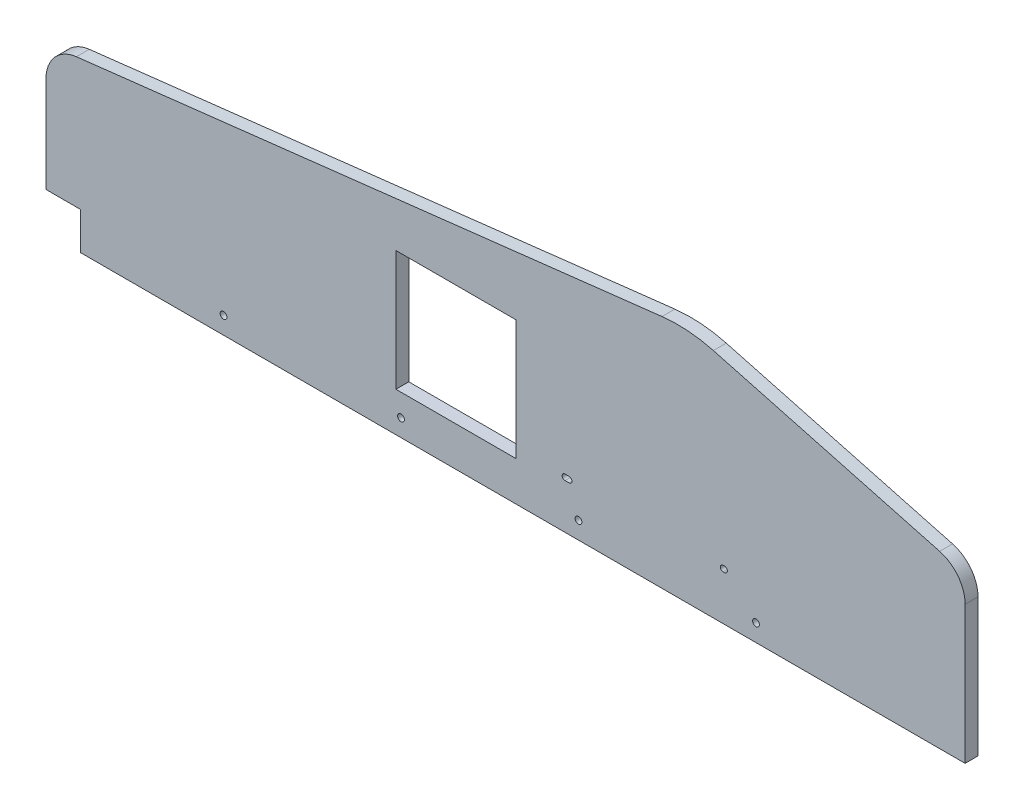
SolidWorks part; units mm, degrees
material "PC High Viscosity"
ref_plane "Front Plane" through (0, 0, 0) normal (0, 0, 1) x (1, 0, 0)
ref_plane "Top Plane" through (0, 0, 0) normal (0, 1, 0) x (1, 0, 0)
ref_plane "Right Plane" through (0, 0, 0) normal (1, 0, 0) x (0, 0, -1)
sketch "Sketch2" plane through (0, 0, 0) normal (0, 0, 1) x (1, 0, 0)
  line L0 (-340, 26.4) -> (-340, 121.4)
  line L1 (-340, 121.4) -> (135, 176.4)
  line L2 (135, 176.4) -> (340, 121.4)
  line L3 (340, 121.4) -> (340, 26.4)
  line L4 (340, 26.4) -> (340, 0)
  line L6 (340, 0) -> (-340, 0)
  line L7 (-340, 0) -> (-340, 26.4)
  dimension "D1" = 150
  dimension "D2" = 680
  dimension "D3" = 95
  dimension "D4" = 475
  dimension "D8" = 95
  dimension "D9" = 26.4
extrude "Boss-Extrude1" add sketch "Sketch2" along normal mid plane 9.525
fillet "Fillet1" radius 25.4 2 edges at (340, 121.4, 0) (-340, 121.4, 0)
fillet "Fillet2" radius 101.6 1 edges at (135, 176.4, 0)
sketch "Sketch3" plane through (0, 0, 4.7625) normal (0, 0, 1) x (1, 0, 0)
  line L0 (0, 0) -> (0, 192.0016) construction
  line L1 (-340, 0) -> (-314.6, 0)
  line L2 (-340, 0) -> (-340, 27.686)
  line L3 (-340, 27.686) -> (-314.6, 27.686)
  line L4 (-314.6, 0) -> (-314.6, 27.686)
  line L5 (0, 192.0016) -> (0, -60.0751) construction
  dimension "D1" = 25.4
  dimension "D2" = 27.686
extrude "Cut-Extrude1" cut sketch "Sketch3" against normal through all
sketch "Sketch5" plane through (0, 0, 4.7625) normal (0, 0, 1) x (1, 0, 0)
  line L0 (-314.6, 0) -> (340, 0) construction
  line L3 (-81.1185, 29.1465) -> (7.7815, 29.1465)
  line L5 (7.7815, 29.1465) -> (7.7815, 118.0465)
  line L6 (7.7815, 118.0465) -> (-81.1185, 118.0465)
  line L7 (340, 0) -> (340, 101.9164) construction
  line L8 (-81.1185, 29.1465) -> (-81.1185, 118.0465)
  dimension "D1" = 332.2185
  dimension "D3" = 29.1465
extrude "Cut-Extrude2" cut sketch "Sketch5" against normal through all
hole_wizard "Tap Drill for M6x1.0 Tap1" positions "Sketch7" profile "Sketch6" hole size "M6x1.0" standard "ANSI Metric" end condition through all
sketch "Sketch7" plane through (0, 0, 4.7625) normal (0, 0, 1) x (1, 0, 0)
  line L0 (-314.6, 0) -> (340, 0) construction
  line L1 (-340, 98.7713) -> (-340, 27.686) construction
  point P0 (-208.682, 12.7)
  point P2 (-77.364, 12.7)
  point P4 (53.954, 12.7)
  point P6 (185.272, 12.7)
  dimension "D1" = 12.7
  dimension "D2" = 131.318
  dimension "D3" = 131.318
  dimension "D4" = 131.318
  dimension "D5" = 131.318
sketch "Sketch6" plane through (-208.682, 12.7, 4.7625) normal (1, 0, 0) x (0, -1, 0)
  line L0 (0, 0) -> (0, 9.525)
  line L1 (0, 9.525) -> (2.5, 9.525)
  line L2 (2.5, 9.525) -> (2.5, 0)
  line L5 (2.5, 0) -> (0, 0)
  line L11 (0, -6.35) -> (0, 107.95) construction
  dimension "Thru Hole Dia." = 5
  dimension "Thru Hole Depth" = 9.525
sketch "Sketch8" plane through (0, 0, 4.7625) normal (0, 0, 1) x (1, 0, 0)
  line L0 (161, 35.3) -> (162, 35.3) construction
  line L1 (161, 37.4) -> (162, 37.4)
  line L2 (161, 33.2) -> (162, 33.2)
  line L3 (47, 35.3) -> (44, 35.3) construction
  line L4 (47, 33.2) -> (44, 33.2)
  line L5 (47, 37.4) -> (44, 37.4)
  line L6 (-314.6, 0) -> (340, 0) construction
  line L10 (-340, 98.7713) -> (-340, 27.686) construction
  arc A0 (161, 37.4) -> (161, 33.2) centre (161, 35.3) ccw
  arc A1 (162, 33.2) -> (162, 37.4) centre (162, 35.3) ccw
  arc A2 (47, 33.2) -> (47, 37.4) centre (47, 35.3) ccw
  arc A3 (44, 37.4) -> (44, 33.2) centre (44, 35.3) ccw
  point P2 (161.5, 35.3)
  point P9 (45.5, 35.3)
  dimension "D2" = 1
  dimension "D1" = 2.1
  dimension "D3" = 35.3
  dimension "D4" = 384
  dimension "D5" = 115.5
  dimension "D6" = 3
extrude "Cut-Extrude3" cut sketch "Sketch8" against normal through all
